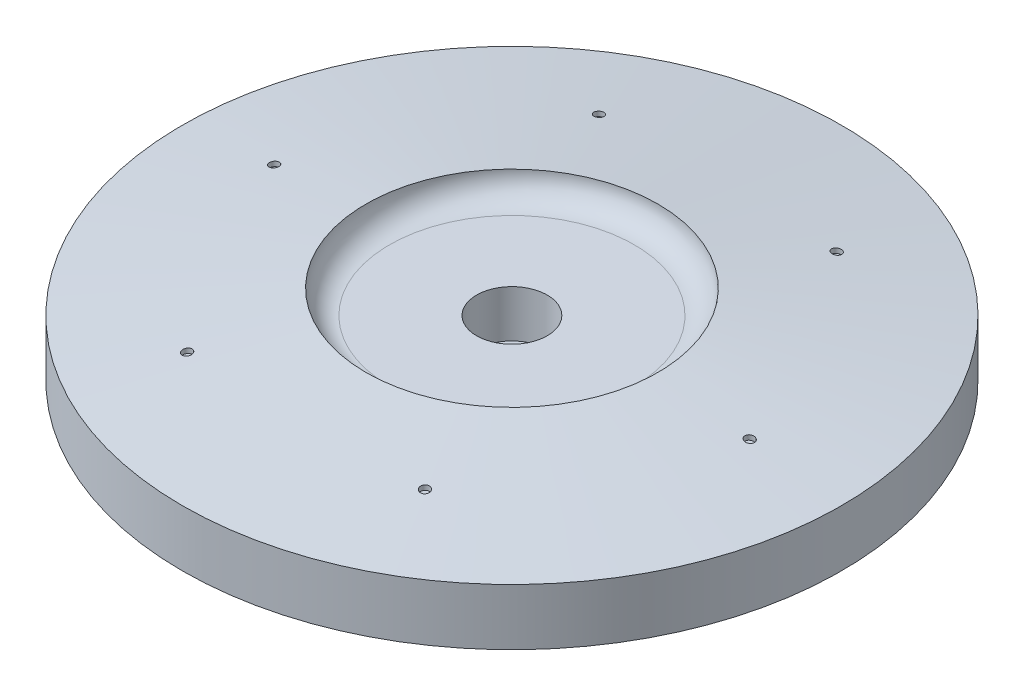
SolidWorks part; units mm, degrees
material "PE High Density"
ref_plane "Front Plane" through (0, 0, 0) normal (0, 0, 1) x (1, 0, 0)
ref_plane "Top Plane" through (0, 0, 0) normal (0, 1, 0) x (1, 0, 0)
ref_plane "Right Plane" through (0, 0, 0) normal (1, 0, 0) x (0, 0, -1)
sketch "Sketch1" plane through (0, 0, 0) normal (0, 1, 0) x (1, 0, 0)
  circle A0 centre (0, 0) radius 88.9
extrude "Boss-Extrude1" add sketch "Sketch1" along normal blind 15.24
sketch "Sketch2" plane through (0, 15.24, 0) normal (0, 1, 0) x (1, 0, 0)
  circle A0 centre (0, 0) radius 39.37
extrude "Boss-Extrude2" add sketch "Sketch2" along normal blind 6.35
sketch "Sketch3" plane through (0, 0, 0) normal (1, 0, 0) x (0, 0, -1)
  line L0 (-39.37, 21.59) -> (-39.37, 15.24)
  line L1 (-39.37, 15.24) -> (-88.9, 15.24)
  line L2 (88.9, 15.24) -> (-88.9, 15.24) construction
  line L3 (-88.9, 15.24) -> (-39.37, 21.59)
  line L4 (0, 0) -> (0, 21.59) construction
  line L5 (39.37, 21.59) -> (-39.37, 21.59) construction
  dimension "D1" = 7.306
revolve "Revolve1" add sketch "Sketch3" angle 360 about L4
sketch "Sketch4" plane through (0, 21.59, 0) normal (0, 1, 0) x (1, 0, 0)
  circle A0 centre (0, 0) radius 39.37
extrude "Cut-Extrude1" cut sketch "Sketch4" against normal blind 6.35
fillet "Fillet1" radius 6.35 1 edges at (0, 15.24, 39.37)
sketch "Sketch5" plane through (0, 15.24, 0) normal (0, 1, 0) x (1, 0, 0)
  circle A0 centre (0, 0) radius 9.525
extrude "Cut-Extrude2" cut sketch "Sketch5" against normal blind 12.7
cosmetic thread "Cosmetic Thread2" parameters "D1"=11.43, "D2"=57.15
sketch "Sketch6" plane through (0, 0, 0) normal (0, -1, 0) x (-1, 0, 0)
  circle A0 centre (0, 0) radius 39.37
shell "Shell1" thickness 1.27 removed face at (0, 2.54, 9.525)
ref_plane "Plane1" through (0, 15.24, 0) normal (0, -1, 0) x (-1, 0, 0)
sketch "Sketch8" plane through (0, 15.24, 0) normal (0, -1, 0) x (-1, 0, 0)
  line L0 (0, 0) -> (0, 98.462) construction
  line L1 (0, 0) -> (0, -98.036) construction
  line L2 (0, 39.37) -> (0, 88.9) construction
  line L3 (-39.37, 0) -> (-88.9, 0) construction
  circle A0 centre (0, 0) radius 39.37 construction
  circle A1 centre (0, 0) radius 88.9 construction
  circle A2 centre (-64.135, 0) radius 1.27
  dimension "D1" = 2.54
extrude "Cut-Extrude3" cut sketch "Sketch8" against normal blind 6.35
pattern_circular "CirPattern1" count 6 every 60 about axis through (0, 15.24, 0) along (0, 1, 0) of "Cut-Extrude3"
sketch "Sketch9" plane through (0, 0, 0) normal (0, -1, 0) x (1, 0, 0)
  circle A0 centre (0, 0) radius 12.7
  dimension "D1" = 25.4
extrude "Boss-Extrude3" add sketch "Sketch9" along normal blind 12.7
cosmetic thread "Cosmetic Thread3" parameters "D2"=24.4
